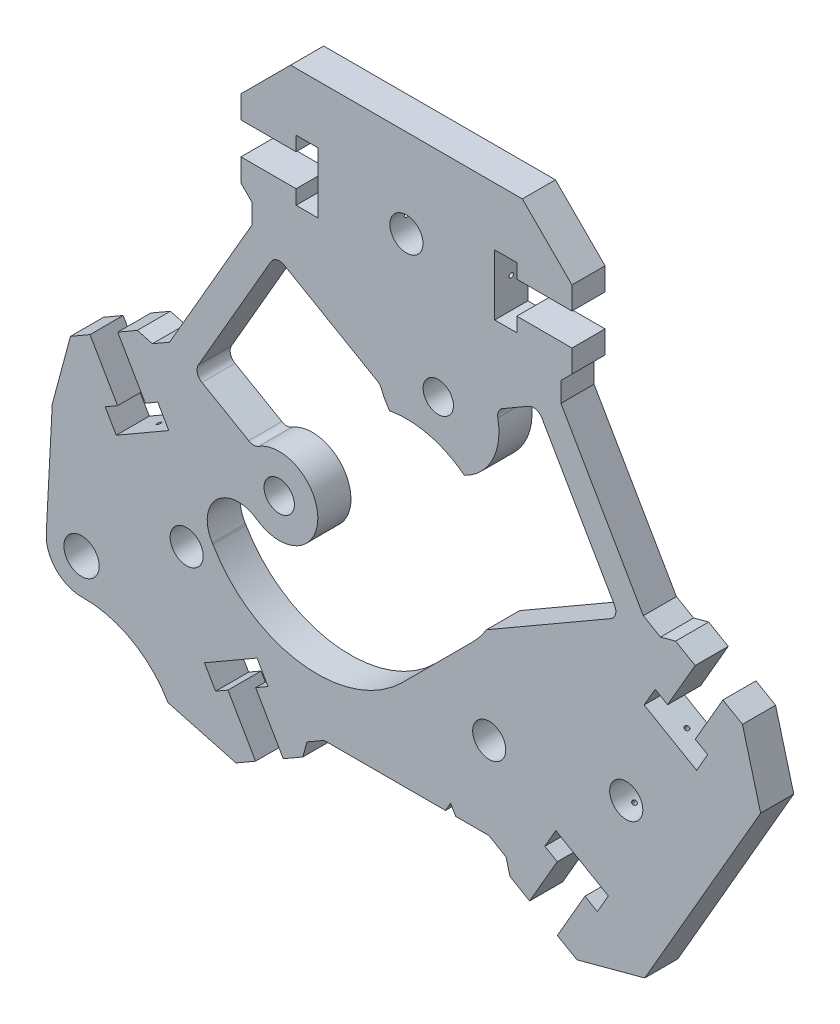
SolidWorks part; units mm, degrees
material "6061-T6 Black anodised"
ref_plane "Front Plane" through (0, 0, 0) normal (0, 0, 1) x (1, 0, 0)
ref_plane "Top Plane" through (0, 0, 0) normal (0, 1, 0) x (1, 0, 0)
ref_plane "Right Plane" through (0, 0, 0) normal (1, 0, 0) x (0, 0, -1)
sketch "Sketch1" plane through (0, 0, 0) normal (0, 0, 1) x (1, 0, 0)
  line L0 (8, 23) -> (8, 25.75)
  line L1 (0, -20.4762) -> (7.4659, -20.4762)
  line L2 (9.0215, -21.3744) -> (7.4659, -20.4762)
  line L3 (9.3875, -22.7404) -> (9.0215, -21.3744)
  line L4 (11.1628, -23.7654) -> (9.3875, -22.7404)
  line L5 (13.6628, -19.4353) -> (11.1628, -23.7654)
  line L6 (12.537, -18.7853) -> (13.6628, -19.4353)
  line L7 (8, 25.75) -> (10, 25.75)
  line L8 (10, 25.75) -> (10, 24.45)
  line L9 (13.537, -17.0532) -> (12.537, -18.7853)
  line L10 (0, 0) -> (0, 23) construction
  line L11 (-15, 23) -> (15, 23) construction
  line L12 (-8, 23) -> (-8, 20.25)
  line L13 (-8, 20.25) -> (-10, 20.25)
  line L14 (10, 20.25) -> (10, 21.55)
  line L15 (8, 20.25) -> (10, 20.25)
  line L16 (-10, 20.25) -> (-10, 21.55)
  line L17 (-10, 21.55) -> (-15, 21.55)
  line L18 (-15, 21.55) -> (-15, 19.5)
  line L19 (-15, 19.5) -> (-14, 18.5)
  line L20 (-14, 18.5) -> (-14, 16.7038)
  line L21 (8, 23) -> (8, 20.25)
  line L22 (15.9186, -18.4282) -> (13.537, -17.0532)
  line L23 (-15, 24.45) -> (-15, 26.5)
  line L24 (15.9186, -18.4282) -> (18.3002, -19.8032)
  line L25 (-10, 24.45) -> (-15, 24.45)
  line L26 (-10, 25.75) -> (-10, 24.45)
  line L27 (18.3002, -19.8032) -> (17.3002, -21.5353)
  line L28 (17.3002, -21.5353) -> (16.1743, -20.8853)
  line L29 (-8, 25.75) -> (-10, 25.75)
  line L30 (-8, 23) -> (-8, 25.75)
  line L31 (0, 23) -> (0, 31) construction
  line L32 (-15, 26.5) -> (-10.5, 31)
  line L33 (-10.5, 31) -> (10.5, 31)
  line L34 (14, 18.5) -> (14, 16.7038)
  line L35 (15, 19.5) -> (14, 18.5)
  line L36 (15, 21.55) -> (15, 19.5)
  line L37 (10, 21.55) -> (15, 21.55)
  line L38 (16.1743, -20.8853) -> (13.6743, -25.2154)
  line L39 (13.6743, -25.2154) -> (15.4497, -26.2404)
  line L40 (15.4497, -26.2404) -> (21.5968, -24.5933)
  line L41 (32.0968, -6.4067) -> (21.5968, -24.5933)
  line L42 (30.4497, -0.2596) -> (32.0968, -6.4067)
  line L43 (28.6743, 0.7654) -> (30.4497, -0.2596)
  line L44 (26.1743, -3.5647) -> (28.6743, 0.7654)
  line L45 (27.3002, -4.2147) -> (26.1743, -3.5647)
  line L46 (26.3002, -5.9468) -> (27.3002, -4.2147)
  line L47 (23.9186, -4.5718) -> (26.3002, -5.9468)
  line L48 (23.9186, -4.5718) -> (21.537, -3.1968)
  line L49 (21.537, -3.1968) -> (22.537, -1.4647)
  line L50 (22.537, -1.4647) -> (23.6628, -2.1147)
  line L51 (10, 24.45) -> (15, 24.45)
  line L52 (15, 24.45) -> (15, 26.5)
  line L53 (15, 26.5) -> (10.5, 31)
  line L54 (23.6628, -2.1147) -> (26.1628, 2.2154)
  line L55 (26.1628, 2.2154) -> (24.3875, 3.2404)
  line L56 (24.3875, 3.2404) -> (23.0215, 2.8744)
  line L57 (23.0215, 2.8744) -> (21.4659, 3.7725)
  line L58 (21.4659, 3.7725) -> (17.7329, 10.2381)
  line L59 (-17.7329, 10.2381) -> (-21.4659, 3.7725)
  line L60 (-23.0215, 2.8744) -> (-21.4659, 3.7725)
  line L61 (-24.3875, 3.2404) -> (-23.0215, 2.8744)
  line L62 (-26.1628, 2.2154) -> (-24.3875, 3.2404)
  line L63 (-23.6628, -2.1147) -> (-26.1628, 2.2154)
  line L64 (-22.537, -1.4647) -> (-23.6628, -2.1147)
  line L65 (-21.537, -3.1968) -> (-22.537, -1.4647)
  line L66 (-23.9186, -4.5718) -> (-21.537, -3.1968)
  line L67 (-23.9186, -4.5718) -> (-26.3002, -5.9468)
  line L68 (-26.3002, -5.9468) -> (-27.3002, -4.2147)
  line L69 (-27.3002, -4.2147) -> (-26.1743, -3.5647)
  line L70 (-26.1743, -3.5647) -> (-28.6743, 0.7654)
  line L71 (-28.6743, 0.7654) -> (-30.4497, -0.2596)
  line L72 (-30.4497, -0.2596) -> (-32.0968, -6.4067)
  line L73 (-21.5968, -24.5933) -> (-32.0968, -6.4067)
  line L74 (-15.4497, -26.2404) -> (-21.5968, -24.5933)
  line L75 (-13.6743, -25.2154) -> (-15.4497, -26.2404)
  line L76 (-16.1743, -20.8853) -> (-13.6743, -25.2154)
  line L77 (-17.3002, -21.5353) -> (-16.1743, -20.8853)
  line L78 (-18.3002, -19.8032) -> (-17.3002, -21.5353)
  line L79 (-15.9186, -18.4282) -> (-18.3002, -19.8032)
  line L80 (-15.9186, -18.4282) -> (-13.537, -17.0532)
  line L81 (-13.537, -17.0532) -> (-12.537, -18.7853)
  line L82 (-12.537, -18.7853) -> (-13.6628, -19.4353)
  line L83 (-13.6628, -19.4353) -> (-11.1628, -23.7654)
  line L84 (-11.1628, -23.7654) -> (-9.3875, -22.7404)
  line L85 (-9.3875, -22.7404) -> (-9.0215, -21.3744)
  line L86 (-9.0215, -21.3744) -> (-7.4659, -20.4762)
  line L87 (-7.4659, -20.4762) -> (0, -20.4762)
  line L136 (-14, 16.7038) -> (-17.7329, 10.2381)
  line L138 (17.7329, 10.2381) -> (14, 16.7038)
  line L139 (0, 0) -> (0, -20.4762) construction
  line L140 (0, 0) -> (17.7329, 10.2381) construction
  line L141 (0, 0) -> (-17.7329, 10.2381) construction
  circle A0 centre (0, 23) radius 1.5
  circle A1 centre (19.9186, -11.5) radius 1.5
  circle A2 centre (0, 0) radius 1.6 construction
  circle A3 centre (-19.9186, -11.5) radius 1.5
  point P0 (0, 0)
  point P32 (-8, 23)
  point P102 (0, 0)
  point P106 (0, 0)
  point P148 (0, 0)
  dimension "D4" = 3
  dimension "D5" = 3
  dimension "D2" = 120
  dimension "D3" = 2
  dimension "D6" = 5
  dimension "D7" = 2.9
  dimension "D9" = 5.5
  dimension "D11" = 30
  dimension "D14" = 23
  dimension "D15" = 7
  dimension "D16" = 45
  dimension "D17" = 8
  dimension "D18" = 1
extrude "Boss-Extrude1" add sketch "Sketch1" along normal blind 3
sketch "Sketch2" plane through (8, 0, 0) normal (1, 0, 0) x (0, 0, -1)
  line L0 (-3, 23) -> (0, 23) construction
  line L3 (-1.5, 24.45) -> (-1.5, 23) construction
  line L4 (-3, 24.45) -> (0, 24.45) construction
  line L6 (0, 20.25) -> (0, 25.75) construction
  circle A0 centre (-1.5, 23) radius 0.2
  dimension "D1" = 0.4
extrude "Cut-Extrude1" cut sketch "Sketch2" against normal through all
ref_axis "Axis1" through (0, 0, -0.25) along (0, 0, 1)
pattern_circular "CirPattern1" count 3 every 120 about axis through (0, 0, -0.25) along (0, 0, 1) of "Cut-Extrude1"
sketch "Sketch3" plane through (0, 0, 3) normal (0, 0, 1) x (1, 0, 0)
  line L1 (-14, 14) -> (14, 14) construction
  line L2 (-14, 14) -> (-14, -14) construction
  line L3 (-14, -14) -> (14, -14) construction
  line L4 (14, 14) -> (14, -14) construction
  line L5 (-14, 14) -> (14, -14) construction
  line L6 (-14, -14) -> (14, 14) construction
  circle A0 centre (0, 0) radius 8.5
  circle A1 centre (-14, -14) radius 1.6 construction
  circle A2 centre (-14, 14) radius 1.6 construction
  circle A3 centre (14, 14) radius 1.6 construction
  circle A4 centre (14, -14) radius 1.6 construction
  dimension "D1" = 3.2
  dimension "D3" = 17
  dimension "D2" = 28
extrude "Cut-Extrude2" cut sketch "Sketch3" against normal through all
sketch "Sketch4" plane through (0, 0, 3) normal (0, 0, 1) x (1, 0, 0)
  line L0 (0, 0) -> (-6.0104, 6.0104) construction
  line L1 (7.5, 12.9904) -> (-7.5, 12.9904) construction
  line L2 (-7.5, 12.9904) -> (-15, 0) construction
  line L3 (-15, 0) -> (-7.5, -12.9904) construction
  line L4 (-7.5, -12.9904) -> (7.5, -12.9904) construction
  line L5 (7.5, -12.9904) -> (15, 0) construction
  line L6 (15, 0) -> (7.5, 12.9904) construction
  line L9 (-12.3365, -0.3156) -> (-14.541, -2.5202) construction
  line L10 (-14.541, -2.5202) -> (-13.7341, -5.5316) construction
  line L11 (-13.7341, -5.5316) -> (-10.7226, -6.3386) construction
  line L12 (-10.7226, -6.3386) -> (-8.5181, -4.134) construction
  line L13 (-8.5181, -4.134) -> (-9.325, -1.1226) construction
  line L14 (-9.325, -1.1226) -> (-12.3365, -0.3156) construction
  line L15 (-6.0104, 6.0104) -> (-16.8625, -4.8417) construction
  line L16 (-7.4659, -20.4762) -> (7.4659, -20.4762) construction
  line L17 (-11.5295, -3.3271) -> (0, 0) construction
  circle A0 centre (0, 0) radius 12.9904 construction
  circle A1 centre (-7.5, 12.9904) radius 1.5 construction
  circle A2 centre (7.5, 12.9904) radius 1.5 construction
  circle A3 centre (15, 0) radius 1.5 construction
  circle A4 centre (7.5, -12.9904) radius 1.5
  circle A5 centre (-7.5, -12.9904) radius 1.5 construction
  circle A6 centre (-15, 0) radius 1.5 construction
  circle A7 centre (8.6461, -8.3213) radius 1.375 construction
  circle A8 centre (0, 0) radius 8.5 construction
  circle A9 centre (-11.5295, -3.3271) radius 1.375
  circle A10 centre (8.6461, -8.3213) radius 3.5 construction
  circle A11 centre (2.8834, 11.6484) radius 1.375
  circle A12 centre (-11.5295, -3.3271) radius 2.7 construction
  point P2 (19.9186, -11.5)
  point P22 (0, 0)
  point P31 (0, 0)
  dimension "D2" = 3
  dimension "D4" = 17
  dimension "D5" = 7
  dimension "D6" = 2.75
  dimension "D8" = 5.4
  dimension "D1" = 15
  dimension "D9" = 45
  dimension "D10" = 12
  dimension "D3" = 6
  dimension "D7" = 3
extrude "Cut-Extrude3" cut sketch "Sketch4" against normal through all
sketch "Sketch8" plane through (0, 0, 0) normal (0, 0, -1) x (-1, 0, 0)
  line L0 (21.537, -3.1968) -> (13.537, -17.0532) construction
  line L1 (12.2799, 14.683) -> (18.8558, 3.2932)
  line L2 (11.0642, 15.0088) -> (2.6441, 10.1475)
  line L3 (21.537, -3.1968) -> (15.2176, -3.1968) construction
  line L4 (15.2176, -3.1968) -> (6.0104, 6.0104) construction
  line L5 (-6.0104, -6.0104) -> (0.3649, -12.3857)
  line L6 (-12.2799, 14.683) -> (-18.8558, 3.2932)
  line L7 (7.4659, -20.4762) -> (-7.4659, -20.4762) construction
  line L8 (15.2176, -8.4805) -> (15.2176, -3.1968) construction
  line L9 (-18.5301, 2.0775) -> (-7.2519, -4.434)
  line L10 (-11.0642, 15.0088) -> (-8.709, 13.649)
  line L11 (18.5301, 2.0775) -> (14.292, -0.3694)
  line L12 (14, 16.7038) -> (21.4659, 3.7725) construction
  line L13 (-21.4659, 3.7725) -> (-14, 16.7038) construction
  arc A0 (12.2799, 14.683) -> (11.0642, 15.0088) centre (11.5092, 14.238) ccw
  arc A1 (-6.0104, -6.0104) -> (-7.2519, -4.434) centre (0, 0) cw
  circle A2 centre (0, 0) radius 8.5 construction
  arc A3 (17.537, -10.125) -> (0.3649, -12.3857) centre (8.0836, -4.6671) cw
  arc A4 (17.6048, -10.0138) -> (17.537, -10.125) centre (19.9186, -11.5) ccw
  arc A5 (17.6048, -10.0138) -> (13.5665, -6.1733) centre (15.2176, -8.4805) ccw
  arc A6 (18.5301, 2.0775) -> (18.8558, 3.2932) centre (18.0851, 2.8482) ccw
  arc A7 (13.3772, -0.3545) -> (14.292, -0.3694) centre (13.847, 0.4014) ccw
  arc A8 (2.2573, 9.6931) -> (2.6441, 10.1475) centre (3.0891, 9.3767) cw
  arc A9 (-11.0642, 15.0088) -> (-12.2799, 14.683) centre (-11.5092, 14.238) ccw
  arc A10 (-18.8558, 3.2932) -> (-18.5301, 2.0775) centre (-18.0851, 2.8482) ccw
  circle A11 centre (0, 0) radius 8.5 construction
  arc A12 (1.5266, 8.3618) -> (2.2573, 9.6931) centre (-2.8834, 11.6484) ccw
  arc A13 (13.3772, -0.3545) -> (13.5665, -6.1733) centre (11.5295, -3.3271) ccw
  arc A14 (1.5266, 8.3618) -> (-5.251, 6.6841) centre (0, 0) ccw
  arc A15 (-8.2806, 12.7069) -> (-5.251, 6.6841) centre (-2.8834, 11.6484) ccw
  arc A16 (-8.709, 13.649) -> (-8.2806, 12.7069) centre (-9.154, 12.8782) cw
  dimension "D2" = 5.5
  dimension "D3" = 0.89
  dimension "D1" = 135
  dimension "D4" = 2.5
  dimension "D5" = 2.5
extrude "Cut-Extrude6" cut sketch "Sketch8" against normal through all
sketch "Sketch10" plane through (0, 0, 0) normal (0, 0, -1) x (-1, 0, 0)
  line L0 (19.9186, -11.5) -> (29.4449, -17) construction
  line L2 (32.0968, -6.4067) -> (32.6405, -16.8334)
  line L3 (32.0968, -6.4067) -> (21.5968, -24.5933)
  circle A0 centre (29.4449, -17) radius 1.6
  arc A1 (29.3822, -20.1994) -> (32.6405, -16.8334) centre (29.4449, -17) ccw
  arc A2 (21.5968, -24.5933) -> (29.3822, -20.1994) centre (29.2101, -28.9888) cw
  dimension "D1" = 3.2
  dimension "D3" = 3.2
  dimension "D2" = 3
extrude "Boss-Extrude3" add sketch "Sketch10" against normal through all
sketch "Sketch11" plane through (0, 0, 0) normal (0, 0, -1) x (-1, 0, 0)
  line L0 (-4.4619, -20.4762) -> (-3.5381, -20.4762)
  line L1 (7.4659, -20.4762) -> (-7.4659, -20.4762) construction
  line L2 (-3.5381, -20.4762) -> (-4, -19.6762)
  line L3 (-4, -19.6762) -> (-4.4619, -20.4762)
  dimension "D1" = 4
  dimension "D2" = 0.8
extrude "Cut-Extrude7" cut sketch "Sketch11" against normal through all
equation "\"D5@Sketch8\"=\"D4@Sketch8\""
